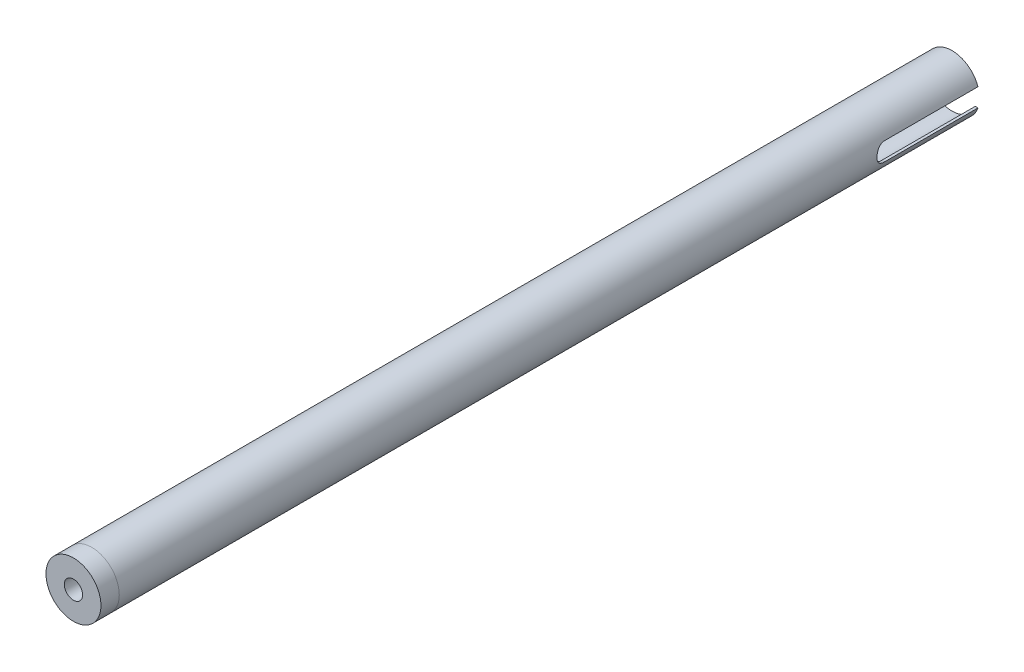
SolidWorks part; units mm, degrees
material "AISI 4130 Steel, normalized at 870C"
ref_plane "Front Plane" through (0, 0, 0) normal (0, 0, 1) x (1, 0, 0)
ref_plane "Top Plane" through (0, 0, 0) normal (0, 1, 0) x (1, 0, 0)
ref_plane "Right Plane" through (0, 0, 0) normal (1, 0, 0) x (0, 0, -1)
sketch "Axis" plane through (0, 0, 0) normal (0, 1, 0) x (1, 0, 0)
  line L0 (0, 0) -> (0, 304.3801) construction
  line L1 (0, 0) -> (0, -21.9075) construction
  line L2 (0, 304.3801) -> (-9.525, 304.3801) construction
  line L5 (0, 332.3201) -> (-22.1542, 267.3343) construction
  dimension "D1" = 21.9075
  dimension "D2" = 9.525
sketch "Sketch1" plane through (0, 0, 0) normal (0, 0, 1) x (1, 0, 0)
  line L0 (-9.525, 0) -> (9.525, 0) construction
  line L1 (-8.9803, 3.175) -> (8.9803, 3.175)
  line L2 (-8.9803, -3.175) -> (8.9803, -3.175)
  circle A0 centre (0, 0) radius 9.525
  circle A1 centre (0, 0) radius 8.636
  circle A2 centre (0, 0) radius 3.175
  dimension "D1" = 19.05
  dimension "D3" = 6.35
  dimension "D2" = 0.889
  dimension "D4" = 6.35
extrude "Threaded insert 1-1" add sketch "Sketch1" against normal blind 6.35 contours A2 L1 A1 | A1 L1 A0 | A2 L0 A1 L1 | A1 L0 A0 L1 | L0 A1 L2 A0 | L0 A2 L2 A1 | A2 L2 A1 | A1 L2 A0 | L0 A1 L2 A2 | L0 A0 L2 A1 | A0 L0 A1 L1 | A1 L0 A2 L1 region at (5.4259, 1.6615, 0) region at (5.4259, -1.6615, 0) region at (8.8881, 1.6046, 0) region at (8.8881, -1.6046, 0) region at (-5.4259, -1.6615, 0) region at (-5.4259, 1.6615, 0) region at (0, 5.4321, 0) region at (0, -5.4321, 0) region at (0, 8.8265, 0) region at (8.5057, -3.3655, 0) region at (-8.8881, -1.6046, 0) region at (-8.8881, 1.6046, 0)
extrude "Threaded insert 1-2" add sketch "Sketch1<3>" against normal blind 6.35 from surface contours A2 L1 A1 | A2 L0 A1 L1 | L0 A2 L2 A1 | A2 L2 A1 | L0 A1 L2 A2 | A1 L0 A2 L1 region at (5.4259, 1.6615, 0) region at (5.4259, -1.6615, 0) region at (-5.4259, -1.6615, 0) region at (-5.4259, 1.6615, 0) region at (0, 5.4321, 0) region at (0, -5.4321, 0) starting at face at (9.525, 0, -6.35)
sketch "Sketch1<3>" plane through (0, 0, 0) normal (0, 0, 1) x (1, 0, 0) same geometry as "Sketch1"
extrude "A-arm tube" add sketch "Sketch1<4>" against normal up to vertex (304.3801 mm away) from surface separate body contours A1 L1 A0 | A1 L0 A0 L1 | L0 A1 L2 A0 | A1 L2 A0 | L0 A0 L2 A1 | A0 L0 A1 L1 region at (8.8881, 1.6046, 0) region at (8.8881, -1.6046, 0) region at (0, 8.8265, 0) region at (8.5057, -3.3655, 0) region at (-8.8881, -1.6046, 0) region at (-8.8881, 1.6046, 0) up to point (0, 0, -304.3801) starting at face at (8.636, 0, -6.35)
sketch "Sketch1<4>" plane through (0, 0, 0) normal (0, 0, 1) x (1, 0, 0) same geometry as "Sketch1"
extrude "Apex slot" cut sketch "Sketch1<5>" along normal blind 35.56 from surface contours A0 L0 A1 L1 | L0 A0 L2 A1 | A1 L0 A0 L1 | L0 A1 L2 A0 region at (8.8881, 1.6046, 0) region at (8.8881, -1.6046, 0) region at (-8.8881, -1.6046, 0) region at (-8.8881, 1.6046, 0) starting at face at (8.636, 0, -304.3801)
sketch "Sketch1<5>" plane through (0, 0, 0) normal (0, 0, 1) x (1, 0, 0) same geometry as "Sketch1"
fillet "Fillet1" radius 3.175 4 edges at (-8.5057, 3.175, -268.8201) (-8.5057, -3.175, -268.8201) (8.5057, -3.175, -268.8201) (8.5057, 3.175, -268.8201)
equation "\"tube diameter\"= 3 / 4"
equation "\"tube thickness\"= .035"
equation "\"apex thickness\"= .25"
equation "\"tube slot\"= 1.4"
equation "\"D1@Sketch1\"=\"tube diameter\""
equation "\"D2@Sketch1\"=\"tube thickness\""
equation "\"threaded insert hole\"= 1 / 4"
equation "\"D3@Sketch1\"=\"threaded insert hole\""
equation "\"D4@Sketch1\"=\"apex thickness\""
equation "\"D1@Apex slot\" = \"tube slot\""
equation "\"D1@Fillet1\"=\"apex thickness\"/2"
equation "\"D2@Axis\"=\"tube diameter\"/2"
